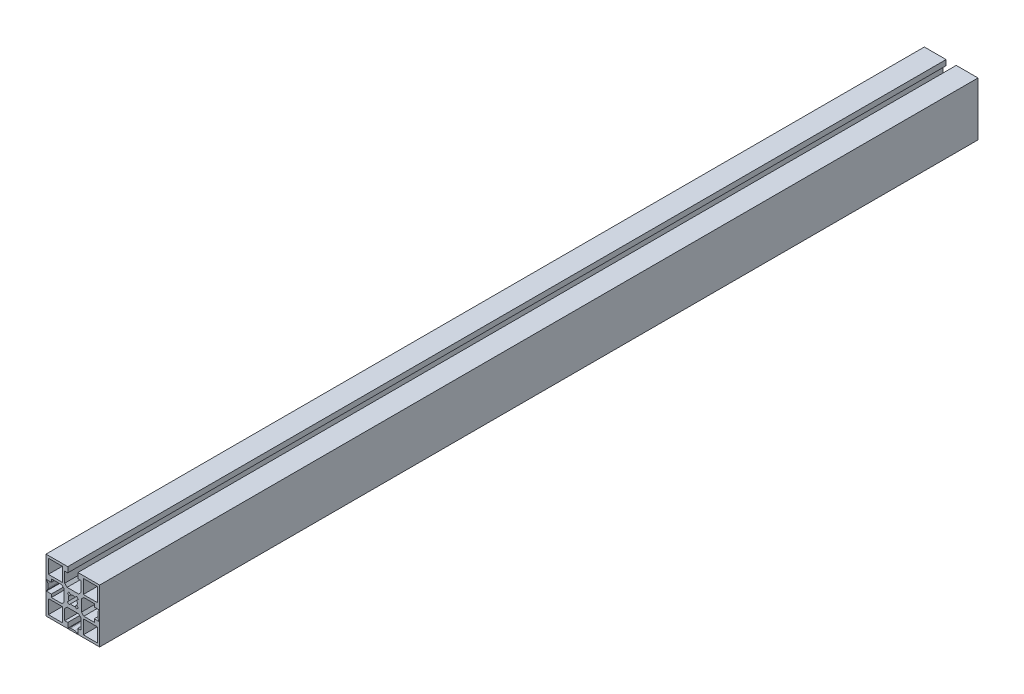
SolidWorks part; units mm, degrees
material "6061 Alloy"
ref_plane "Front Plane" through (0, 0, 0) normal (0, 0, 1) x (1, 0, 0)
ref_plane "Top Plane" through (0, 0, 0) normal (0, 1, 0) x (1, 0, 0)
ref_plane "Right Plane" through (0, 0, 0) normal (1, 0, 0) x (0, 0, -1)
sketch "Sketch1" plane through (0, 0, 0) normal (0, 0, 1) x (1, 0, 0)
  line L0 (-4.2495, 22.1993) -> (-4.2495, 22.4993)
  line L1 (-4.2495, 22.4993) -> (-4.2495, 22.1993)
  line L2 (4.2505, 22.1993) -> (4.2505, 22.4993)
  line L3 (4.2505, 22.4993) -> (4.2505, 22.1993)
  line L8 (-22.4995, -22.5007) -> (22.5005, -22.5007)
  line L9 (22.5005, -22.5007) -> (22.5005, 22.4993)
  line L10 (22.5005, 22.4993) -> (-22.4995, 22.4993)
  line L11 (-22.4995, 22.4993) -> (-22.4995, -22.5007)
  line L24 (-20.4995, -20.5007) -> (-20.4995, -8.8007)
  line L25 (-8.7996, -20.5007) -> (-20.4995, -20.5007)
  line L26 (-8.7996, -8.8007) -> (-8.7996, -20.5007)
  line L27 (-20.4995, -8.8007) -> (-8.7996, -8.8007)
  line L28 (8.8005, -20.5008) -> (8.8005, -8.8008)
  line L29 (20.5005, -20.5008) -> (8.8005, -20.5008)
  line L30 (20.5005, -8.8008) -> (20.5005, -20.5008)
  line L31 (8.8005, -8.8008) -> (20.5005, -8.8008)
  line L32 (20.5006, 8.7993) -> (8.8006, 8.7993)
  line L33 (20.5006, 20.4993) -> (20.5006, 8.7993)
  line L34 (8.8006, 20.4993) -> (20.5006, 20.4993)
  line L35 (8.8006, 8.7993) -> (8.8006, 20.4993)
  line L36 (-8.7995, 20.4993) -> (-8.7995, 8.7993)
  line L37 (-8.7995, 8.7993) -> (-20.4995, 8.7993)
  line L38 (-20.4995, 8.7993) -> (-20.4995, 20.4993)
  line L39 (-20.4995, 20.4993) -> (-8.7995, 20.4993)
  line L54 (-22.1995, -3.9507) -> (-21.7318, -3.483)
  line L55 (-22.1995, -4.2507) -> (-22.1995, -3.9507)
  line L56 (-17.9995, -4.2507) -> (-22.1995, -4.2507)
  line L57 (-17.9995, -6.8007) -> (-17.9995, -4.2507)
  line L58 (-9.1995, -6.8007) -> (-17.9995, -6.8007)
  line L59 (-7.1995, -4.8007) -> (-9.1995, -6.8007)
  line L60 (-7.1995, 4.7993) -> (-7.1995, -4.8007)
  line L61 (-9.1995, 6.7993) -> (-7.1995, 4.7993)
  line L62 (-17.9995, 6.7993) -> (-9.1995, 6.7993)
  line L63 (-17.9995, 4.2493) -> (-17.9995, 6.7993)
  line L64 (-22.1995, 4.2493) -> (-17.9995, 4.2493)
  line L65 (-22.1995, 3.9493) -> (-22.1995, 4.2493)
  line L66 (-21.7317, 3.4815) -> (-22.1995, 3.9493)
  line L67 (-20.9995, -1.7152) -> (-20.9995, 1.7137)
  line L82 (-6.7995, -18.0007) -> (-6.7995, -9.2007)
  line L83 (-4.2495, -18.0007) -> (-6.7995, -18.0007)
  line L84 (-4.2495, -22.2007) -> (-4.2495, -18.0007)
  line L85 (-3.9495, -22.2007) -> (-4.2495, -22.2007)
  line L86 (-3.4817, -21.733) -> (-3.9495, -22.2007)
  line L87 (1.715, -21.0007) -> (-1.7139, -21.0007)
  line L88 (3.9505, -22.2007) -> (3.4828, -21.733)
  line L89 (4.2505, -22.2007) -> (3.9505, -22.2007)
  line L90 (4.2505, -18.0007) -> (4.2505, -22.2007)
  line L91 (6.8005, -18.0007) -> (4.2505, -18.0007)
  line L92 (6.8005, -9.2007) -> (6.8005, -18.0007)
  line L93 (4.8005, -7.2007) -> (6.8005, -9.2007)
  line L94 (-4.7995, -7.2007) -> (4.8005, -7.2007)
  line L95 (-6.7995, -9.2007) -> (-4.7995, -7.2007)
  line L110 (7.2005, -4.8007) -> (7.2005, 4.7993)
  line L111 (9.2005, -6.8007) -> (7.2005, -4.8007)
  line L112 (18.0005, -6.8007) -> (9.2005, -6.8007)
  line L113 (18.0005, -4.2507) -> (18.0005, -6.8007)
  line L114 (22.2005, -4.2507) -> (18.0005, -4.2507)
  line L115 (22.2005, -3.9507) -> (22.2005, -4.2507)
  line L116 (21.7327, -3.4829) -> (22.2005, -3.9507)
  line L117 (21.0005, 1.7138) -> (21.0005, -1.7151)
  line L118 (22.2005, 3.9493) -> (21.7328, 3.4816)
  line L119 (22.2005, 4.2493) -> (22.2005, 3.9493)
  line L120 (18.0005, 4.2493) -> (22.2005, 4.2493)
  line L121 (18.0005, 6.7993) -> (18.0005, 4.2493)
  line L122 (9.2005, 6.7993) -> (18.0005, 6.7993)
  line L123 (7.2005, 4.7993) -> (9.2005, 6.7993)
  line L138 (-4.7995, 7.1993) -> (-6.7995, 9.1993)
  line L139 (4.8005, 7.1993) -> (-4.7995, 7.1993)
  line L140 (6.8005, 9.1993) -> (4.8005, 7.1993)
  line L141 (6.8005, 17.9993) -> (6.8005, 9.1993)
  line L142 (4.2505, 17.9993) -> (6.8005, 17.9993)
  line L143 (4.2505, 22.1993) -> (4.2505, 17.9993)
  line L144 (3.9505, 22.1993) -> (4.2505, 22.1993)
  line L145 (3.4828, 21.7316) -> (3.9505, 22.1993)
  line L146 (-1.7139, 20.9993) -> (1.715, 20.9993)
  line L147 (-3.9495, 22.1993) -> (-3.4817, 21.7315)
  line L148 (-4.2495, 22.1993) -> (-3.9495, 22.1993)
  line L149 (-4.2495, 17.9993) -> (-4.2495, 22.1993)
  line L150 (-6.7995, 17.9993) -> (-4.2495, 17.9993)
  line L151 (-6.7995, 9.1993) -> (-6.7995, 17.9993)
  line L164 (-4.5957, -3.1827) -> (-3.2622, -1.8492)
  line L165 (-3.1815, -4.5969) -> (-4.5957, -3.1827)
  line L166 (-1.848, -3.2635) -> (-3.1815, -4.5969)
  line L167 (3.1825, -4.5969) -> (1.849, -3.2635)
  line L168 (4.5967, -3.1827) -> (3.1825, -4.5969)
  line L169 (3.2633, -1.8492) -> (4.5967, -3.1827)
  line L170 (4.5967, 3.1813) -> (3.2633, 1.8478)
  line L171 (3.1825, 4.5955) -> (4.5967, 3.1813)
  line L172 (1.849, 3.262) -> (3.1825, 4.5955)
  line L173 (-3.1815, 4.5955) -> (-1.848, 3.262)
  line L174 (-4.5957, 3.1813) -> (-3.1815, 4.5955)
  line L175 (-3.2622, 1.8478) -> (-4.5957, 3.1813)
  arc A2 (-21.7318, -3.483) -> (-20.9995, -1.7152) centre (-23.4995, -1.7152) ccw
  arc A3 (-20.9995, 1.7137) -> (-21.7317, 3.4815) centre (-23.4995, 1.7137) ccw
  arc A6 (-1.7139, -21.0007) -> (-3.4817, -21.733) centre (-1.7139, -23.5007) ccw
  arc A7 (3.4828, -21.733) -> (1.715, -21.0007) centre (1.715, -23.5007) ccw
  arc A10 (21.0005, -1.7151) -> (21.7327, -3.4829) centre (23.5005, -1.7151) ccw
  arc A11 (21.7328, 3.4816) -> (21.0005, 1.7138) centre (23.5005, 1.7138) ccw
  arc A14 (1.715, 20.9993) -> (3.4828, 21.7316) centre (1.715, 23.4993) ccw
  arc A15 (-3.4817, 21.7315) -> (-1.7139, 20.9993) centre (-1.7139, 23.4993) ccw
  arc A20 (-1.848, -3.2635) -> (1.849, -3.2635) centre (0.0005, -0.0007) ccw
  arc A21 (3.2633, -1.8492) -> (3.2633, 1.8478) centre (0.0005, -0.0007) ccw
  arc A22 (1.849, 3.262) -> (-1.848, 3.262) centre (0.0005, -0.0007) ccw
  arc A23 (-3.2622, 1.8478) -> (-3.2622, -1.8492) centre (0.0005, -0.0007) ccw
extrude "Boss-Extrude1" add sketch "Sketch1" along normal blind 736.6 contours L10 L11 L8 L9 A23 L175 L174 L173 A22 L172 L171 L170 A21 L169 L168 L167 A20 L166 L165 L164 L24 L27 L26 L25 L28 L31 L30 L29 L32 L35 L34 L33 L38 L39 L36 L37 L67 A3 L66 L65 L64 L63 L62 L61 L60 region at (-4.8859, 20.0993, 0)
